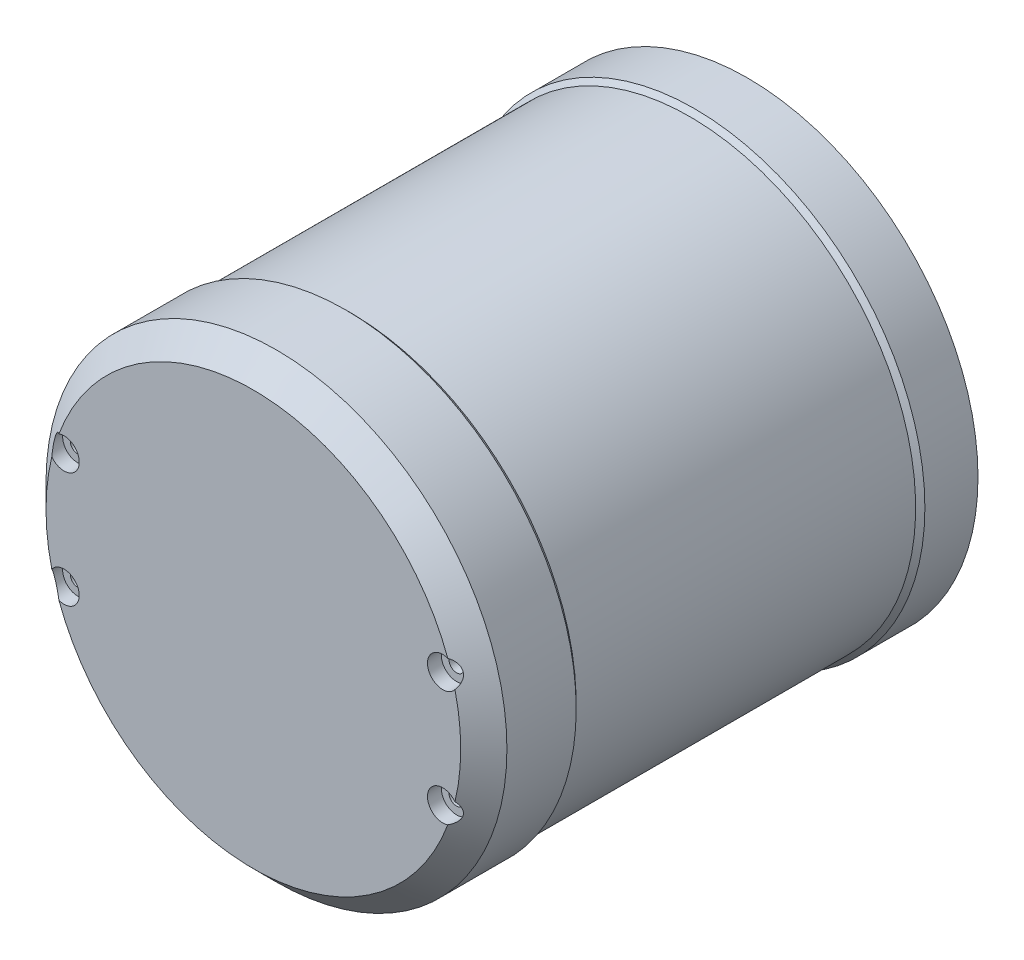
SolidWorks part; units mm, degrees
ref_plane "Front Plane" through (0, 0, 0) normal (0, 0, 1) x (1, 0, 0)
ref_plane "Top Plane" through (0, 0, 0) normal (0, 1, 0) x (1, 0, 0)
ref_plane "Right Plane" through (0, 0, 0) normal (1, 0, 0) x (0, 0, -1)
sketch "Sketch1" plane through (0, 0, 0) normal (0, 0, 1) x (1, 0, 0)
  circle A1 centre (0, 55) radius 47.5
  circle A2 centre (0, 55) radius 49.9
  circle A3 centre (0, 55) radius 49.9
  arc A4 (-37, 84.306) -> (-37, 25.694) centre (0, 55) ccw construction
  dimension "D2" = 0.3
  dimension "D1" = 0.3
extrude "Boss-Extrude1" add sketch "Sketch1" against normal up to surface (100 mm away)
sketch "Sketch2" plane through (0, 0, 0) normal (0, 0, 1) x (1, 0, 0)
  circle A0 centre (0, 55) radius 49.9 construction
  circle A1 centre (0, 55) radius 49.9
  circle A2 centre (41, 67.5) radius 1.65
  circle A3 centre (41, 42.5) radius 1.65
  circle A4 centre (-41, 67.5) radius 1.65
  circle A5 centre (-41, 42.5) radius 1.65
  circle A6 centre (41, 67.5) radius 2.25 construction
  circle A7 centre (41, 42.5) radius 2.25 construction
  circle A8 centre (-41, 67.5) radius 2.25 construction
  circle A9 centre (-41, 42.5) radius 2.25 construction
  dimension "D1" = 3.3
extrude "Boss-Extrude2" add sketch "Sketch2" along normal blind 7
sketch "Sketch3" plane through (0, 0, 7) normal (0, 0, 1) x (1, 0, 0)
  circle A0 centre (-41, 67.5) radius 3.3
  circle A1 centre (-41, 42.5) radius 3.3
  circle A2 centre (41, 67.5) radius 3.3
  circle A3 centre (41, 42.5) radius 3.3
  dimension "D1" = 6.6
extrude "Cut-Extrude1" cut sketch "Sketch3" against normal blind 3
chamfer "Chamfer1" distance 5 angle 45 1 edges at (49.9, 55, 7)
sketch "Sketch4" plane through (0, 0, 0) normal (1, 0, 0) x (0, 0, -1)
  line L0 (88.5, 88.7868) -> (88.5, 0) construction
  line L1 (88.5, 88.7868) -> (88.5, 0) construction
  line L2 (-2, 5.1) -> (-2, 104.9) construction
  line L3 (-2, 5.1) -> (-2, 104.9) construction
  line L4 (-2, 55) -> (-50002, 55) construction
  line L5 (13, 104.9) -> (14, 103.9)
  line L6 (100, 104.9) -> (-2, 104.9) construction
  line L7 (14, 103.9) -> (87.5, 103.9)
  line L8 (87.5, 103.9) -> (88.5, 104.9)
  line L9 (13, 104.9) -> (88.5, 104.9)
  point P6 (-2, 55)
  point P11 (0, 0)
  dimension "D1" = 135
  dimension "D2" = 135
  dimension "D3" = 15
  dimension "D4" = 1
revolve "Cut-Revolve1" cut sketch "Sketch4" angle 360 about L4
sketch "Sketch5" plane through (0, 0, -100) normal (0, 0, -1) x (-1, 0, 0)
  circle A0 centre (-44, 45) radius 3.3
  circle A1 centre (-44, 65) radius 3.3
  circle A2 centre (44, 45) radius 3.3
  circle A3 centre (44, 65) radius 3.3
  dimension "D1" = 6.6
extrude "Cut-Extrude2" cut sketch "Sketch5" against normal blind 8
